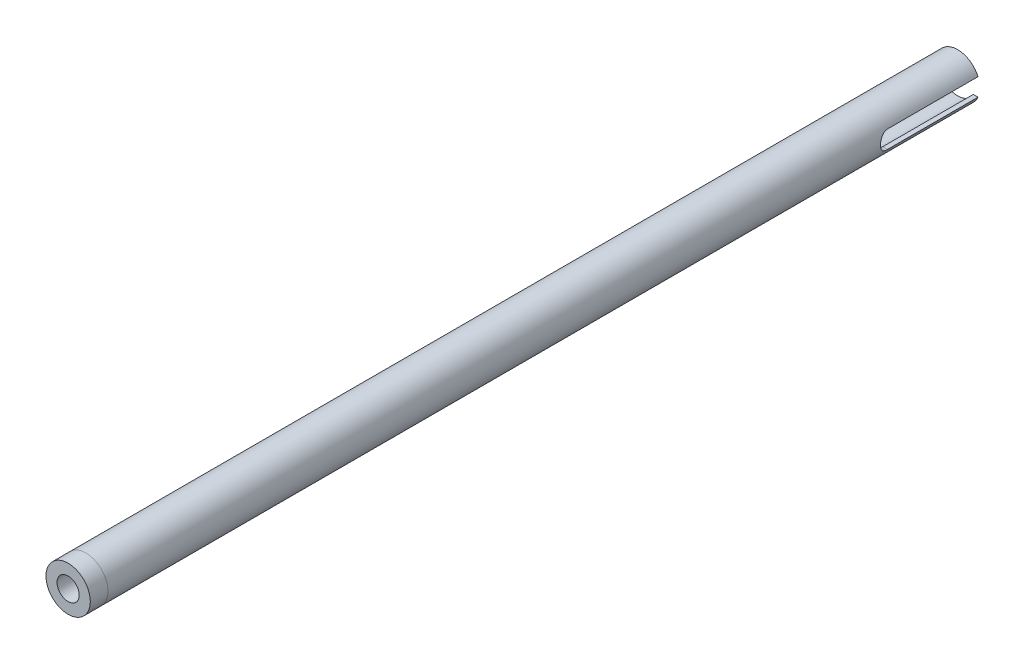
SolidWorks part; units mm, degrees
ref_plane "Front Plane" through (0, 0, 0) normal (0, 0, 1) x (1, 0, 0)
ref_plane "Top Plane" through (0, 0, 0) normal (0, 1, 0) x (1, 0, 0)
ref_plane "Right Plane" through (0, 0, 0) normal (1, 0, 0) x (0, 0, -1)
sketch "Axis" plane through (0, 0, 0) normal (0, 1, 0) x (1, 0, 0)
  line L0 (0, 0) -> (0, 318.4826) construction
  line L1 (0, 0) -> (0, -34.925) construction
  line L2 (0, 318.4826) -> (-7.9375, 318.4826) construction
  line L3 (0, 347.2669) -> (-10.3187, 309.8472) construction
  dimension "D1" = 34.925
  dimension "D2" = 7.9375
sketch "Sketch1" plane through (0, 0, 0) normal (0, 0, 1) x (1, 0, 0)
  line L0 (-7.9375, 0) -> (7.9375, 0) construction
  line L1 (-7.2748, 3.175) -> (7.2748, 3.175)
  line L2 (-7.2748, -3.175) -> (7.2748, -3.175)
  circle A0 centre (0, 0) radius 7.9375
  circle A1 centre (0, 0) radius 6.4135
  circle A2 centre (0, 0) radius 3.9688
  dimension "D1" = 15.875
  dimension "D3" = 7.9375
  dimension "D2" = 1.524
  dimension "D4" = 6.35
extrude "Threaded insert 1-1" add sketch "Sketch1" against normal blind 6.35 contours A2 L1 A1 | A1 L1 A0 | A2 L0 A1 L1 | A1 L0 A0 L1 | L0 A1 L2 A0 | L0 A2 L2 A1 | A2 L2 A1 | A1 L2 A0 | L0 A1 L2 A2 | L0 A0 L2 A1 | A0 L0 A1 L1 | A1 L0 A2 L1 region at (4.7887, 1.6543, 0) region at (4.7887, -1.6543, 0) region at (6.9234, 1.6163, 0) region at (6.9234, -1.6163, 0) region at (-4.7887, -1.6543, 0) region at (-4.7887, 1.6543, 0) region at (0, 4.6159, 0) region at (0, -4.6159, 0) region at (0, 6.5666, 0) region at (6.4237, -3.3281, 0) region at (-6.9234, -1.6163, 0) region at (-6.9234, 1.6163, 0)
extrude "Threaded insert 1-2" add sketch "Sketch1<3>" against normal blind 9.525 from surface contours A2 L1 A1 | A2 L0 A1 L1 | L0 A2 L2 A1 | A2 L2 A1 | L0 A1 L2 A2 | A1 L0 A2 L1 region at (4.7887, 1.6543, 0) region at (4.7887, -1.6543, 0) region at (-4.7887, -1.6543, 0) region at (-4.7887, 1.6543, 0) region at (0, 4.6159, 0) region at (0, -4.6159, 0) starting at face at (7.9375, 0, -6.35)
sketch "Sketch1<3>" plane through (0, 0, 0) normal (0, 0, 1) x (1, 0, 0) same geometry as "Sketch1"
extrude "A-arm tube" add sketch "Sketch1<4>" against normal up to vertex (318.4826 mm away) from surface separate body contours A1 L1 A0 | A1 L0 A0 L1 | L0 A1 L2 A0 | A1 L2 A0 | L0 A0 L2 A1 | A0 L0 A1 L1 region at (6.9234, 1.6163, 0) region at (6.9234, -1.6163, 0) region at (0, 6.5666, 0) region at (6.4237, -3.3281, 0) region at (-6.9234, -1.6163, 0) region at (-6.9234, 1.6163, 0) up to point (0, 0, -318.4826) starting at face at (6.4135, 0, -6.35)
sketch "Sketch1<4>" plane through (0, 0, 0) normal (0, 0, 1) x (1, 0, 0) same geometry as "Sketch1"
extrude "Apex slot" cut sketch "Sketch1<5>" along normal blind 35.56 from surface contours A0 L0 A1 L1 | L0 A0 L2 A1 | A1 L0 A0 L1 | L0 A1 L2 A0 region at (6.9234, 1.6163, 0) region at (6.9234, -1.6163, 0) region at (-6.9234, -1.6163, 0) region at (-6.9234, 1.6163, 0) starting at face at (6.4135, 0, -318.4826)
sketch "Sketch1<5>" plane through (0, 0, 0) normal (0, 0, 1) x (1, 0, 0) same geometry as "Sketch1"
fillet "Fillet1" radius 3.175 4 edges at (-6.4237, 3.175, -282.9226) (-6.4237, -3.175, -282.9226) (6.4237, -3.175, -282.9226) (6.4237, 3.175, -282.9226)
equation "\"tube diameter\"= 5 / 8"
equation "\"tube thickness\"= .06"
equation "\"apex thickness\"= .25"
equation "\"tube slot\"= 1.4"
equation "\"D1@Sketch1\"=\"tube diameter\""
equation "\"D2@Sketch1\"=\"tube thickness\""
equation "\"threaded insert hole\"= .3125"
equation "\"D3@Sketch1\"=\"threaded insert hole\""
equation "\"D4@Sketch1\"=\"apex thickness\""
equation "\"D1@Apex slot\" = \"tube slot\""
equation "\"D1@Fillet1\"=\"apex thickness\"/2"
equation "\"D2@Axis\"=\"tube diameter\"/2"
